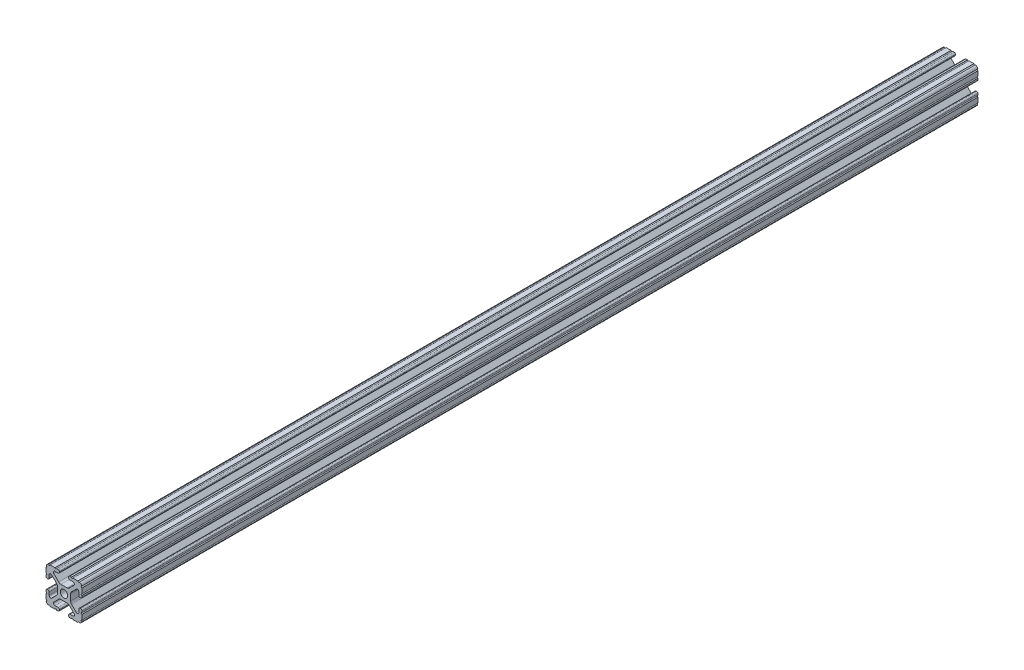
SolidWorks part; units mm, degrees
ref_plane "Front Plane" through (0, 0, 0) normal (0, 0, 1) x (1, 0, 0)
ref_plane "Top Plane" through (0, 0, 0) normal (0, 1, 0) x (1, 0, 0)
ref_plane "Right Plane" through (0, 0, 0) normal (1, 0, 0) x (0, 0, -1)
other "Configuration Table"
sketch "Sketch2" plane through (0, 0, 0) normal (0, 0, 1) x (1, 0, 0)
  line L0 (0, 12.7) -> (0, -12.7) construction
  line L1 (-12.7, 0) -> (12.7, 0) construction
  line L2 (3.2512, -12.7) -> (12.7, -12.7)
  line L3 (12.7, -12.7) -> (12.7, -3.2512)
  line L4 (3.2512, -12.7) -> (3.2512, -10.4902)
  line L5 (3.2512, -10.4902) -> (8.9276, -10.4902)
  line L6 (8.9276, -10.4902) -> (3.0856, -4.6482)
  line L7 (0, 0) -> (12.7, -12.7) construction
  line L8 (12.7, -3.2512) -> (10.4902, -3.2512)
  line L9 (10.4902, -3.2512) -> (10.4902, -8.9276)
  line L10 (10.4902, -8.9276) -> (4.6482, -3.0856)
  circle A0 centre (0, 0) radius 2.6035
  arc A1 (6.3485, -10.4902) -> (7.1039, -8.6665) centre (6.3485, -9.4219) ccw construction
  point P8 (0, -4.6482)
  dimension "Center Hole Diameter" = 5.207
  dimension "Rail Height" = 25.4
  dimension "Rail Width" = 25.4
  dimension "T-Slot Width" = 6.5024
  dimension "Slot Inner Width" = 14.8336
  dimension "Thickness" = 2.2098
  dimension "Slot Depth" = 5.842
  dimension "D1" = 2.2098
sketch "Sketch3" plane through (0, 0, 0) normal (1, 0, 0) x (0, 0, -1)
  line L0 (-316.5, -12.7) -> (316.5, -12.7) construction
  line L1 (-291.1, 0) -> (291.1, 0) construction
  dimension "Length" = 633
sketch "Sketch4" plane through (0, 0, 0) normal (0, 0, 1) x (1, 0, 0)
  line L0 (4.1904, -12.7) -> (10.1173, -12.7)
  line L1 (3.2512, -12.7) -> (12.7, -12.7) construction
  line L2 (3.2512, -12.7) -> (3.2512, -10.4902) construction
  line L3 (3.2512, -10.4902) -> (8.9276, -10.4902) construction
  line L4 (3.2512, -11.4294) -> (3.2512, -11.7608)
  line L5 (4.1904, -10.4902) -> (6.3485, -10.4902)
  line L6 (0, -4.6482) -> (2.164, -4.6482)
  line L7 (8.9276, -10.4902) -> (3.0856, -4.6482) construction
  line L8 (3.7373, -5.2999) -> (7.1039, -8.6665)
  line L9 (12.7, -12.7) -> (12.7, -3.2512) construction
  line L10 (10.4902, -8.9276) -> (4.6482, -3.0856) construction
  line L11 (10.4902, -3.2512) -> (10.4902, -8.9276) construction
  line L12 (10.4902, -6.3485) -> (10.4902, -4.1904)
  line L13 (12.7, -3.2512) -> (10.4902, -3.2512) construction
  line L14 (11.4294, -3.2512) -> (11.7608, -3.2512)
  line L15 (12.7, -4.1904) -> (12.7, -10.1173)
  line L16 (8.6665, -7.1039) -> (5.2999, -3.7373)
  line L17 (4.6482, 0) -> (4.6482, -2.164)
  line L18 (-12.7, 0) -> (12.7, 0) construction
  line L19 (0, -4.6482) -> (0, -2.6035)
  line L20 (0, 12.7) -> (0, -12.7) construction
  line L21 (4.6482, 0) -> (2.6035, 0)
  arc A0 (3.2512, -11.7608) -> (4.1904, -12.7) centre (4.1904, -11.7608) ccw
  arc A2 (3.2512, -11.4294) -> (4.1904, -10.4902) centre (4.1904, -11.4294) cw
  arc A3 (6.3485, -10.4902) -> (7.1039, -8.6665) centre (6.3485, -9.4219) ccw
  arc A4 (2.164, -4.6482) -> (3.7373, -5.2999) centre (2.164, -6.8732) cw
  arc A5 (10.1173, -12.7) -> (12.7, -10.1173) centre (10.1173, -10.1173) ccw
  arc A6 (8.6665, -7.1039) -> (10.4902, -6.3485) centre (9.4219, -6.3485) ccw
  arc A7 (10.4902, -4.1904) -> (11.4294, -3.2512) centre (11.4294, -4.1904) cw
  arc A8 (11.7608, -3.2512) -> (12.7, -4.1904) centre (11.7608, -4.1904) cw
  arc A9 (5.2999, -3.7373) -> (4.6482, -2.164) centre (6.8732, -2.164) cw
  circle A10 centre (0, 0) radius 2.6035 construction
  arc A11 (0, -2.6035) -> (2.6035, 0) centre (0, 0) ccw
  dimension "D1" = 2.5827
  dimension "D2" = 2.225
  dimension "D3" = 0.9392
extrude "Boss-Extrude1" add sketch "Sketch4" along normal mid plane 633
sketch "Sketch5" plane through (0, 0, 0) normal (0, 0, 1) x (1, 0, 0)
  line L0 (3.2512, -12.7) -> (12.7, -12.7) construction
  line L1 (4.1904, -10.4902) -> (6.3485, -10.4902) construction
  line L3 (0, 0) -> (12.7, -12.7) construction
  line L4 (6.3485, -10.4902) -> (6.3485, -12.7) construction
  line L5 (8.9276, -10.4902) -> (3.0856, -4.6482) construction
  circle A0 centre (10.3562, -12.7) radius 0.5524
  circle A1 centre (5.796, -12.7) radius 0.5524
  circle A2 centre (12.7, -10.3562) radius 0.5524
  circle A3 centre (12.7, -5.796) radius 0.5524
  point P10 (5.2694, -10.4902)
  point P12 (9.4219, -6.3485)
  dimension "D1" = 1.1049
extrude "Cut-Extrude1" cut sketch "Sketch5" against normal through all both and the other way through all
mirror "Mirror1" about plane through (0, 0, 0) normal (1, 0, 0) of bodies 137 134
mirror "Mirror2" about plane through (0, 0, 0) normal (0, 1, 0) of bodies 135
equation "\"D1@Boss-Extrude1\"=\"Length@Sketch3\""
equation "\"D1@Sketch2\"=\"Thickness@Sketch2\""
equation "\"D2@Sketch4\"=\"Slot Inner Width@Sketch2\"*0.15"
equation "\"D1@Sketch4\"=\"D3@Sketch4\"*2.75"
equation "\"D3@Sketch4\"=\"Thickness@Sketch2\"*0.425"
equation "\"D1@Sketch5\"=\"Thickness@Sketch2\"*0.5"
